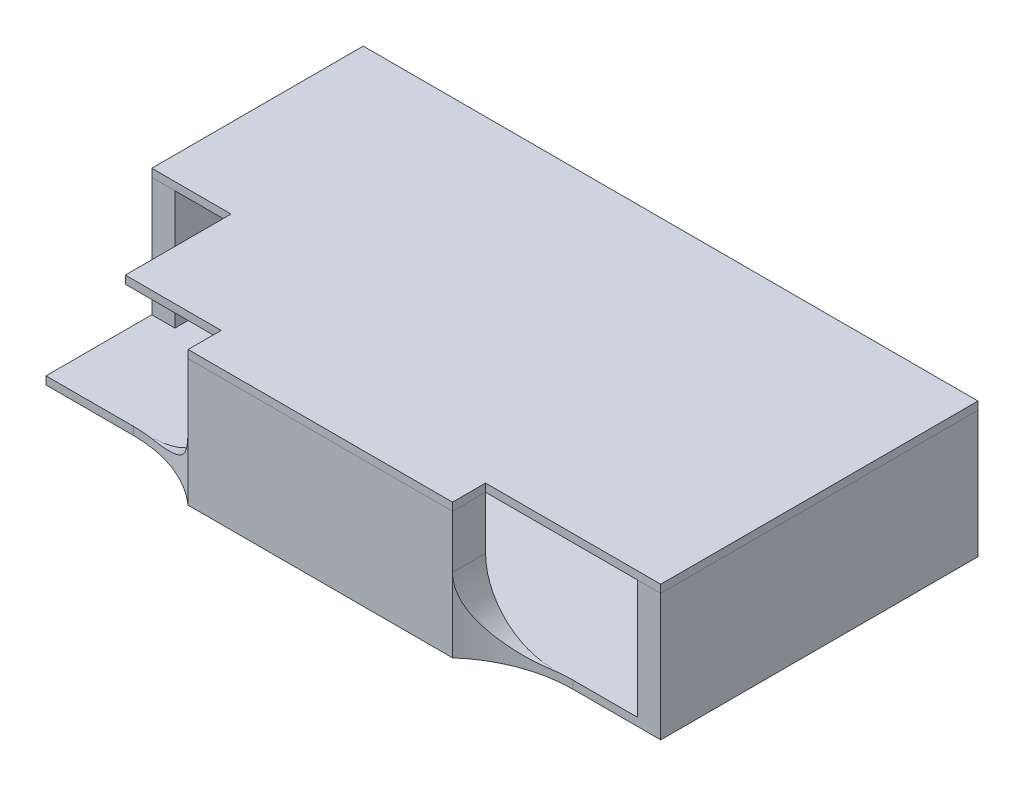
SolidWorks part; units mm, degrees
material "PEI"
ref_plane "Front Plane" through (0, 0, 0) normal (0, 0, 1) x (1, 0, 0)
ref_plane "Top Plane" through (0, 0, 0) normal (0, 1, 0) x (1, 0, 0)
ref_plane "Right Plane" through (0, 0, 0) normal (1, 0, 0) x (0, 0, -1)
sketch "Sketch6" plane through (0, 0, 0) normal (0, 1, 0) x (1, 0, 0)
  line L1 (23.25, -12) -> (-23.25, -12)
  line L2 (23.25, -12) -> (23.25, 12)
  line L3 (23.25, 12) -> (-23.25, 12)
  line L4 (-23.25, -12) -> (-23.25, 12)
  line L5 (23.25, -12) -> (-23.25, 12) construction
  line L6 (23.25, 12) -> (-23.25, -12) construction
  point P0 (0, 0)
  dimension "D1" = 24
  dimension "D2" = 46.5
extrude "Boss-Extrude4" add sketch "Sketch6" along normal blind 0.6
sketch "Sketch7" plane through (0, 0.6, 0) normal (0, 1, 0) x (1, 0, 0)
  line L0 (-23.25, -12) -> (23.25, -12) construction
  line L1 (23.25, 12) -> (21.5, 12)
  line L2 (23.25, 12) -> (23.25, -12)
  line L3 (23.25, -12) -> (21.5, -12)
  line L4 (21.5, 12) -> (21.5, -12)
  line L7 (-23.25, 12) -> (-21.5, 12)
  line L8 (-23.25, 12) -> (-23.25, -4)
  line L9 (-23.25, -4) -> (-21.5, -4)
  line L10 (-21.5, 12) -> (-21.5, -4)
  point P12 (-22.375, -4)
  dimension "D1" = 43
  dimension "D2" = 1.75
  dimension "D3" = 8
extrude "Boss-Extrude5" add sketch "Sketch7" along normal blind 9
sketch "Sketch8" plane through (0, 0, 12) normal (0, 0, 1) x (1, 0, 0)
  line L0 (-23.25, 0) -> (23.25, 0) construction
  line L1 (-10, 0) -> (10, 0)
  line L2 (-10, 0) -> (-10, 9.6)
  line L3 (-10, 9.6) -> (10, 9.6)
  line L4 (10, 0) -> (10, 9.6)
  line L5 (21.5, 9.6) -> (23.25, 9.6) construction
  dimension "D1" = 20
  dimension "D2" = 10
extrude "Boss-Extrude6" add sketch "Sketch8" along normal blind 2.5
fillet "Fillet1" radius 10 2 edges at (-10, 0.3, 12) (10, 0.3, 12)
fillet "Fillet2" radius 5 2 edges at (-10, 0.6, 13.25) (10, 0.6, 13.25)
sketch "Sketch10" plane through (0, 9.6, 0) normal (0, 1, 0) x (1, 0, 0)
  line L0 (-23.25, -12) -> (-16.6144, -12) construction
  line L1 (-23.25, 12) -> (23.25, 12)
  line L2 (-23.25, 12) -> (-23.25, -4)
  line L3 (-17.25, -12) -> (-10, -12)
  line L4 (23.25, 12) -> (23.25, -12)
  line L5 (-23.25, 12) -> (-23.25, -4) construction
  line L6 (-23.25, -4) -> (-17.25, -4)
  line L7 (-17.25, -4) -> (-17.25, -12)
  line L8 (-23.25, -4) -> (-21.5, -4) construction
  line L9 (-15, -12) -> (15, -12) construction
  line L10 (-10, -12) -> (-10, -14.5)
  line L11 (-10, -14.5) -> (10, -14.5)
  line L12 (10, -14.5) -> (10, -12)
  line L13 (10, -12) -> (23.25, -12)
  dimension "D1" = 6
extrude "Boss-Extrude12" add sketch "Sketch10" along normal blind 0.6 separate body
equation "\"D2@Sketch8\"=\"D1@Sketch8\"/2"
